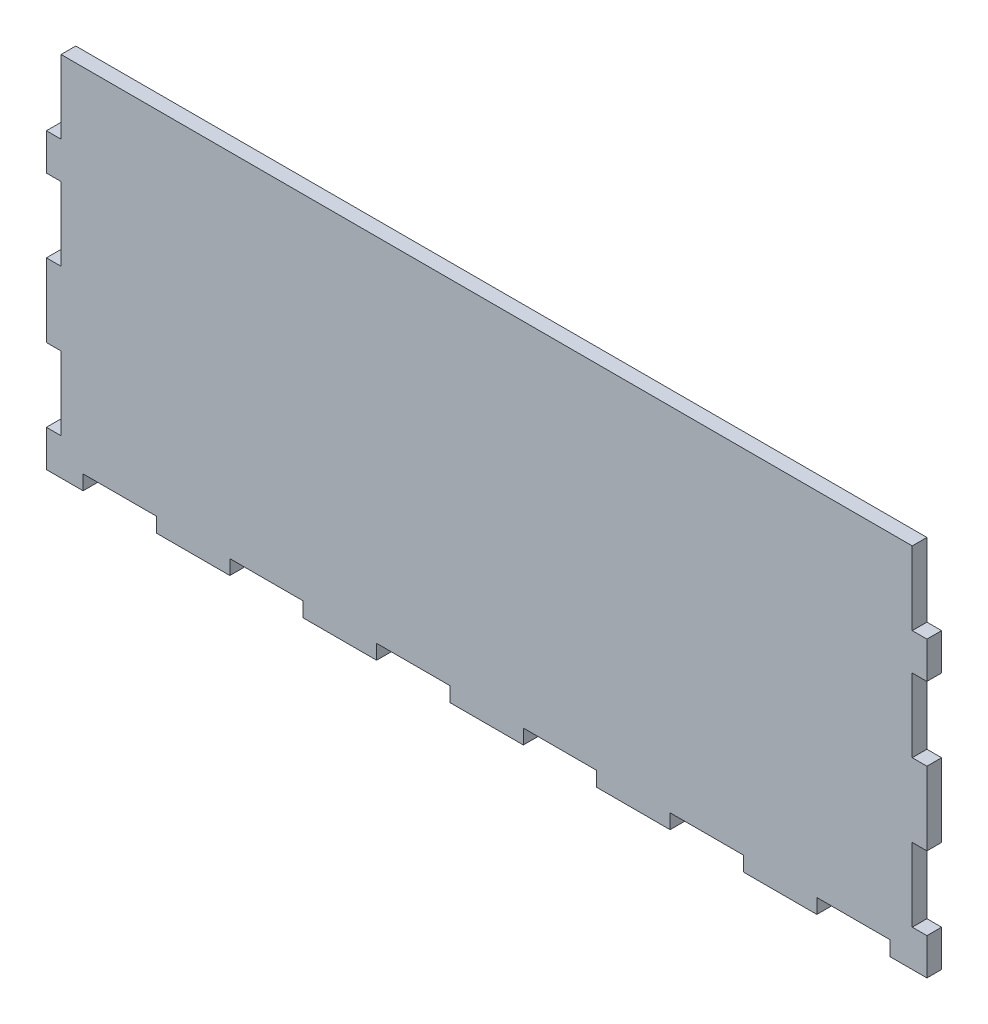
SolidWorks part; units mm, degrees
ref_plane "Front Plane" through (0, 0, 0) normal (0, 0, 1) x (1, 0, 0)
ref_plane "Top Plane" through (0, 0, 0) normal (0, 1, 0) x (1, 0, 0)
ref_plane "Right Plane" through (0, 0, 0) normal (1, 0, 0) x (0, 0, -1)
sketch "Sketch1" plane through (0, 0, 0) normal (0, 0, 1) x (1, 0, 0)
  line L0 (0, 0) -> (0, -127) construction
  line L1 (152.4, 0) -> (-152.4, 0) construction
  line L2 (12.7, -127) -> (-12.7, -127)
  line L3 (-12.7, -127) -> (-12.7, -121.92)
  line L4 (-12.7, -121.92) -> (-38.1, -121.92)
  line L5 (-38.1, -121.92) -> (-38.1, -127)
  line L6 (-38.1, -127) -> (-63.5, -127)
  line L7 (-63.5, -127) -> (-63.5, -121.92)
  line L8 (-63.5, -121.92) -> (-88.9, -121.92)
  line L9 (-88.9, -121.92) -> (-88.9, -127)
  line L10 (-88.9, -127) -> (-114.3, -127)
  line L11 (-152.4, -127) -> (-152.4, -114.3)
  line L12 (-114.3, -127) -> (-114.3, -121.92)
  line L13 (-114.3, -121.92) -> (-139.7, -121.92)
  line L14 (-139.7, -121.92) -> (-139.7, -127)
  line L15 (-139.7, -127) -> (-152.4, -127)
  line L16 (-152.4, -114.3) -> (-147.32, -114.3)
  line L17 (-147.32, -114.3) -> (-147.32, -88.9)
  line L18 (-147.32, -88.9) -> (-152.4, -88.9)
  line L19 (-152.4, -63.5) -> (-147.32, -63.5)
  line L20 (-147.32, -63.5) -> (-147.32, -38.1)
  line L21 (-147.32, -38.1) -> (-152.4, -38.1)
  line L22 (-152.4, -25.4) -> (-147.32, -25.4)
  line L23 (-147.32, -25.4) -> (-147.32, 0)
  line L24 (-152.4, -88.9) -> (-152.4, -63.5)
  line L25 (-152.4, -38.1) -> (-152.4, -25.4)
  line L26 (152.4, -38.1) -> (152.4, -25.4)
  line L27 (152.4, -88.9) -> (152.4, -63.5)
  line L28 (147.32, -25.4) -> (147.32, 0)
  line L29 (152.4, -25.4) -> (147.32, -25.4)
  line L30 (147.32, -38.1) -> (152.4, -38.1)
  line L31 (147.32, -63.5) -> (147.32, -38.1)
  line L32 (152.4, -63.5) -> (147.32, -63.5)
  line L33 (147.32, -88.9) -> (152.4, -88.9)
  line L34 (147.32, -114.3) -> (147.32, -88.9)
  line L35 (152.4, -114.3) -> (147.32, -114.3)
  line L36 (139.7, -127) -> (152.4, -127)
  line L37 (139.7, -121.92) -> (139.7, -127)
  line L38 (114.3, -121.92) -> (139.7, -121.92)
  line L39 (114.3, -127) -> (114.3, -121.92)
  line L40 (152.4, -127) -> (152.4, -114.3)
  line L41 (88.9, -127) -> (114.3, -127)
  line L42 (88.9, -121.92) -> (88.9, -127)
  line L43 (63.5, -121.92) -> (88.9, -121.92)
  line L44 (63.5, -127) -> (63.5, -121.92)
  line L45 (38.1, -127) -> (63.5, -127)
  line L46 (38.1, -121.92) -> (38.1, -127)
  line L47 (12.7, -121.92) -> (38.1, -121.92)
  line L48 (12.7, -127) -> (12.7, -121.92)
  line L49 (-147.32, 0) -> (147.32, 0)
  dimension "D1" = 152.4
  dimension "D2" = 127
  dimension "D3" = 12.7
  dimension "D4" = 25.4
  dimension "D5" = 5.08
  dimension "D6" = 12.7
  dimension "D7" = 25.4
extrude "Boss-Extrude1" add sketch "Sketch1" along normal mid plane 5.08
